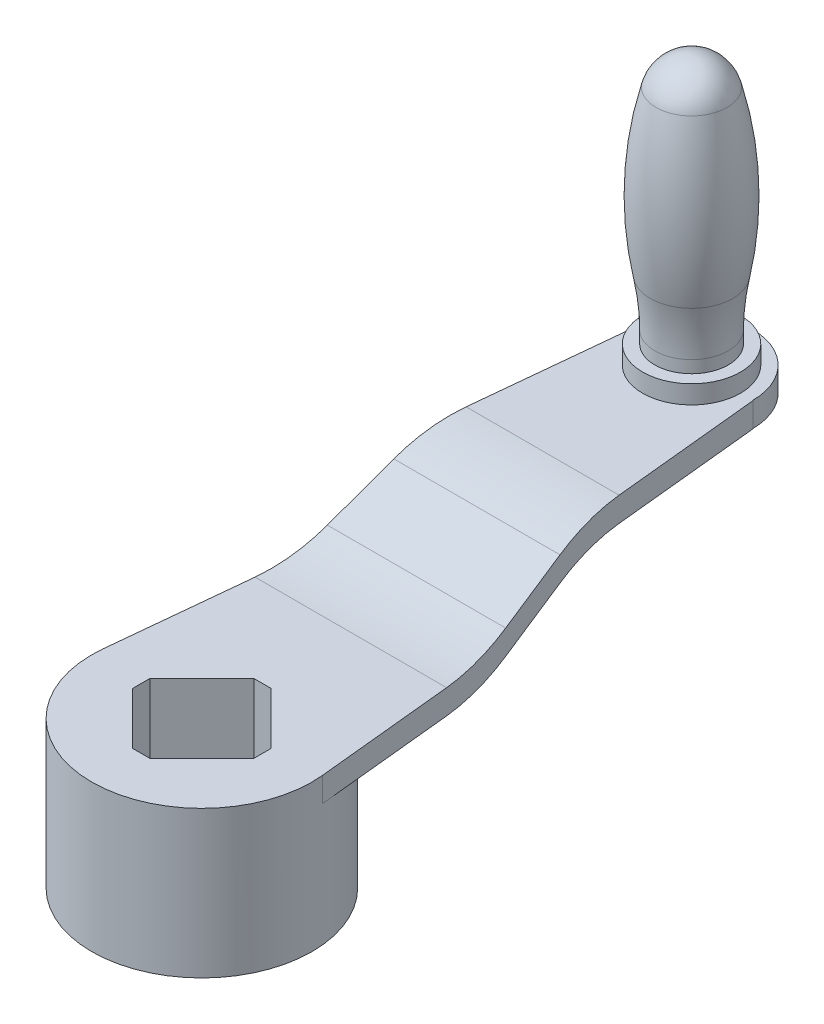
SolidWorks part; units mm, degrees
ref_plane "Ön Düzlem" through (0, 0, 0) normal (0, 0, 1) x (1, 0, 0)
ref_plane "Üst Düzlem" through (0, 0, 0) normal (0, 1, 0) x (1, 0, 0)
ref_plane "Sağ Düzlem" through (0, 0, 0) normal (1, 0, 0) x (0, 0, -1)
sketch "Çizim2" plane through (0, 0, 0) normal (0, 1, 0) x (1, 0, 0)
  circle A0 centre (0, 0) radius 45
  dimension "D1" = 90
extrude "Yükseklik-Ekstrüzyon1" add sketch "Çizim2" against normal blind 60
sketch "Çizim5" plane through (0, 0, 0) normal (0, 1, 0) x (1, 0, 0)
  line L0 (-24.7487, 3.5355) -> (-3.5355, 24.7487)
  line L1 (0, 0) -> (0, 45) construction
  line L2 (0, 0) -> (-45, 0) construction
  line L3 (0, 0) -> (0, -45) construction
  line L4 (0, 0) -> (45, 0) construction
  line L5 (-24.7487, -3.5355) -> (-3.5355, -24.7487)
  line L6 (3.5355, -24.7487) -> (24.7487, -3.5355)
  line L7 (24.7487, 3.5355) -> (3.5355, 24.7487)
  line L8 (-3.5355, 24.7487) -> (3.5355, 24.7487)
  line L9 (-24.7487, -3.5355) -> (-24.7487, 3.5355)
  line L10 (-3.5355, -24.7487) -> (3.5355, -24.7487)
  line L11 (24.7487, -3.5355) -> (24.7487, 3.5355)
  circle A0 centre (0, 0) radius 45 construction
  point P1 (-28.2843, 0)
  point P2 (0, 28.2843)
  point P3 (-29.0016, 0)
  point P4 (0, 0)
  point P10 (0, -28.2843)
  point P14 (28.2843, 0)
  point P15 (0, 33.3458)
  point P16 (26.4319, 0)
  point P17 (0, -26.8602)
  dimension "D3" = 90
  dimension "D1" = 45
  dimension "D2" = 45
  dimension "D4" = 40
  dimension "D5" = 5
  dimension "D6" = 45
  dimension "D7" = 5
  dimension "D8" = 45
  dimension "D9" = 5
  dimension "D10" = 45
  dimension "D11" = 5
  dimension "D12" = 45
extrude "Kes-Ekstrüzyon1" cut sketch "Çizim5" against normal through all
sketch "Çizim6" plane through (0, 0, 0) normal (1, 0, 0) x (0, 0, -1)
  line L0 (-3.5355, 0) -> (3.5355, 0) construction
  line L1 (-3.5355, 0) -> (3.5355, 0)
  line L2 (3.5355, 0) -> (3.5355, -10)
  line L3 (-45, 0) -> (60.8359, 0)
  line L4 (0, 0) -> (200, 0) construction
  line L5 (139.1641, 25) -> (200, 25)
  line L6 (200, 25) -> (200, 0)
  line L7 (87.6687, 6.3344) -> (112.3313, 18.6656)
  line L8 (3.5355, -5) -> (19.9482, -5) construction
  line L9 (-45, 0) -> (-45, -10) construction
  line L10 (-45, 0) -> (-45, -60) construction
  line L11 (-45, -10) -> (60.8359, -10)
  line L12 (139.1641, 15) -> (200, 15)
  line L13 (87.6687, -3.6656) -> (112.3313, 8.6656)
  arc A0 (112.3313, 18.6656) -> (139.1641, 25) centre (139.1641, -35) cw
  arc A1 (60.8359, 0) -> (87.6687, 6.3344) centre (60.8359, 60) ccw
  arc A2 (112.3313, 8.6656) -> (139.1641, 15) centre (139.1641, -45) cw
  arc A3 (60.8359, -10) -> (87.6687, -3.6656) centre (60.8359, 50) ccw
  point P13 (125, 25)
  point P16 (75, 0)
  point P27 (125, 15)
  point P30 (75, -10)
  point P31 (200, 15)
  dimension "D3" = 50
  dimension "D4" = 25
  dimension "D6" = 60
  dimension "D11" = 60
  dimension "D1" = 10
  dimension "D2" = 120
  dimension "D5" = 200
  dimension "D7" = 10
  dimension "D8" = 120
  dimension "D9" = 50
  dimension "D10" = 25
extrude "Yükseklik-Ekstrüzyon2" add sketch "Çizim6" along normal mid plane 90 contours L11 A3 L13 A2 L12 L6 L5 A0 L7 A1 L3 L2 region at (0, 7.7249, -101.7678)
extrude "Kes-Ekstrüzyon2" cut sketch "Çizim5<2>" against normal through all
sketch "Çizim5<2>" plane through (0, 0, 0) normal (0, 1, 0) x (1, 0, 0) same geometry as "Çizim5"
ref_plane "Düzlem1" through (0, 41.8509, 0) normal (0, 1, 0) x (1, 0, 0)
sketch "Çizim7" plane through (0, 41.8509, 0) normal (0, 1, 0) x (1, 0, 0)
  line L0 (0, 0) -> (0, 200) construction
  line L1 (0, 200) -> (-25, 200) construction
  line L2 (0, 200) -> (25, 200) construction
  line L3 (-44.7744, 4.5) -> (-24.8747, 202.5)
  line L4 (-45, 0) -> (-45, 200)
  line L5 (44.7744, 4.5) -> (24.8747, 202.5)
  line L6 (-45, 200) -> (45, 200)
  line L7 (45, 200) -> (45, 0)
  circle A0 centre (0, 200) radius 25
  circle A2 centre (0, 0) radius 45
  dimension "D2" = 50
  dimension "D3" = 90
  dimension "D1" = 200
  dimension "D4" = 200
  dimension "D5" = 200
extrude "Kes-Ekstrüzyon4" cut sketch "Çizim7" against normal through all contours A2 L3 L6 L4 | A2 L7 L6 L5 region at (-38.3756, 41.8509, -134.0795) region at (38.3756, 41.8509, -134.0795)
sketch "Çizim9" plane through (0, 25, 0) normal (0, 1, 0) x (1, 0, 0)
  line L0 (25.1259, 200) -> (-25.1259, 200) construction
  line L1 (-25.1259, 200) -> (25, 200) construction
  arc A0 (25, 200) -> (-25, 200) centre (0, 200) ccw
  line M4 (25.1259, 200) -> (-25.1259, 200)
  dimension "D1" = 50
extrude "Yükseklik-Ekstrüzyon3" add sketch "Çizim9" against normal blind 10 contours A0 M4 region at (0, 25, -210.6103)
sketch "Çizim10" plane through (0, 25, 0) normal (0, 1, 0) x (1, 0, 0)
  circle A0 centre (0, 200) radius 20
  dimension "D1" = 40
extrude "Yükseklik-Ekstrüzyon4" add sketch "Çizim10" along normal blind 7.5
sketch "Çizim12" plane through (0, 0, 0) normal (1, 0, 0) x (0, 0, -1)
  line L0 (220, 32.5) -> (180, 32.5) construction
  line L1 (200, 134.5) -> (200, 119.5)
  line L2 (220, 32.5) -> (180, 32.5)
  line L3 (200, 25) -> (200, 134.5) construction
  line L4 (185, 32.5) -> (185, 37.5)
  line L6 (215, 32.5) -> (215, 37.5)
  line L7 (200, 134.5) -> (200, 32.5)
  line L8 (200, 134.5) -> (200, 119.5)
  arc A1 (215, 37.5) -> (216.8344, 56.9378) centre (318.9, 37.5) cw
  arc A2 (216.8344, 56.9378) -> (214.5019, 123.3333) centre (69.4828, 85) ccw
  arc A5 (214.5019, 123.3333) -> (200, 134.5) centre (200, 119.5) ccw
  point P12 (218.8191, 124.6884)
  point P15 (217.0794, 124.7963)
  point P16 (0, 0)
  point P19 (214.4219, 123.6241)
  dimension "D5" = 150
  dimension "D6" = 15
  dimension "D4" = 85
  dimension "D1" = 109.5
  dimension "D2" = 5
  dimension "D3" = 15
revolve "Döndür5" add sketch "Çizim12" angle 360 about L3 region at (0, 82.2648, -208.5913)
